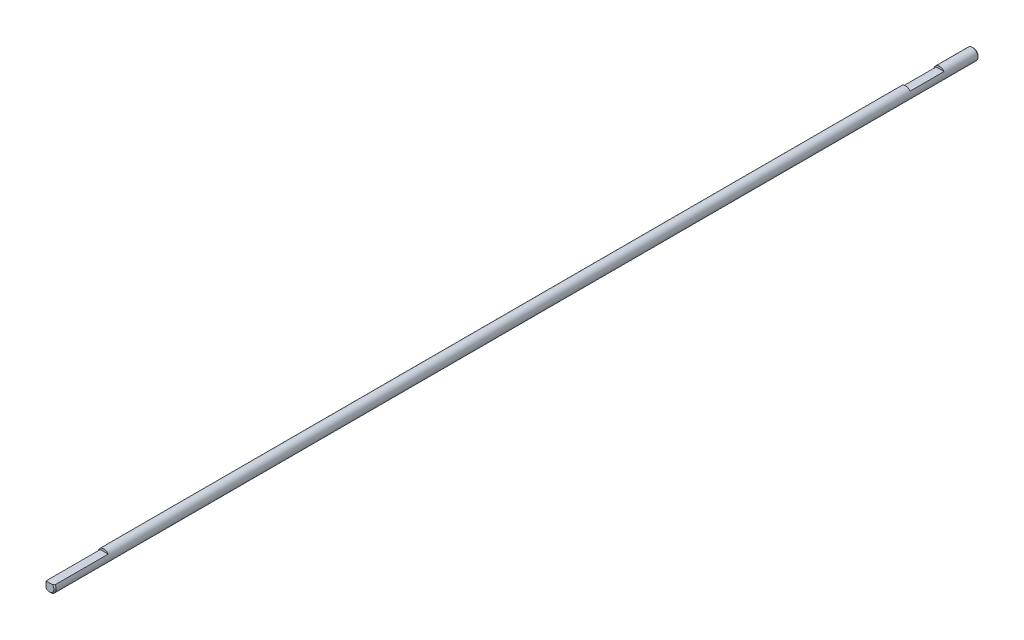
SolidWorks part; units mm, degrees
material "AISI 1020"
ref_plane "Спереди" through (0, 0, 0) normal (0, 0, 1) x (1, 0, 0)
ref_plane "Сверху" through (0, 0, 0) normal (0, 1, 0) x (1, 0, 0)
ref_plane "Справа" through (0, 0, 0) normal (1, 0, 0) x (0, 0, -1)
sketch "Эскиз1" plane through (0, 0, 0) normal (0, 0, 1) x (1, 0, 0)
  circle A0 centre (0, 0) radius 2.5
  dimension "D1" = 5
extrude "Body" add sketch "Эскиз1" along normal blind 408.5
chamfer "ChamferEdges" distance 0.5 angle 45 2 edges at (2.5, 0, 408.5) (2.5, 0, 0)
sketch "Sketch2" plane through (0, 0, 0) normal (1, 0, 0) x (0, 0, -1)
  line L0 (-408.5, 2) -> (-408.5, -2) construction
  line L1 (-30, 4.0099) -> (-15, 4.0099)
  line L2 (-30, 4.0099) -> (-30, 1.5)
  line L3 (-30, 1.5) -> (-15, 1.5)
  line L4 (-15, 4.0099) -> (-15, 1.5)
  line L6 (-408, -2.5) -> (-0.5, -2.5) construction
  line L11 (-384.5, 3.4421) -> (-384.5, 1.5)
  line L13 (-412.5, 3.4421) -> (-384.5, 3.4421)
  line L14 (-412.5, 3.4421) -> (-412.5, 1.5)
  line L15 (-412.5, 1.5) -> (-384.5, 1.5)
  dimension "D1" = 30
  dimension "D2" = 4
  dimension "D3" = 15
  dimension "D4" = 24
extrude "FirstSlots" cut sketch "Sketch2" against normal through all both and the other way through all
pattern_circular "AnotherSlots" count 2 every 90 about axis through (0, 0, 408.5) along (0, 0, 1) of "FirstSlots"
